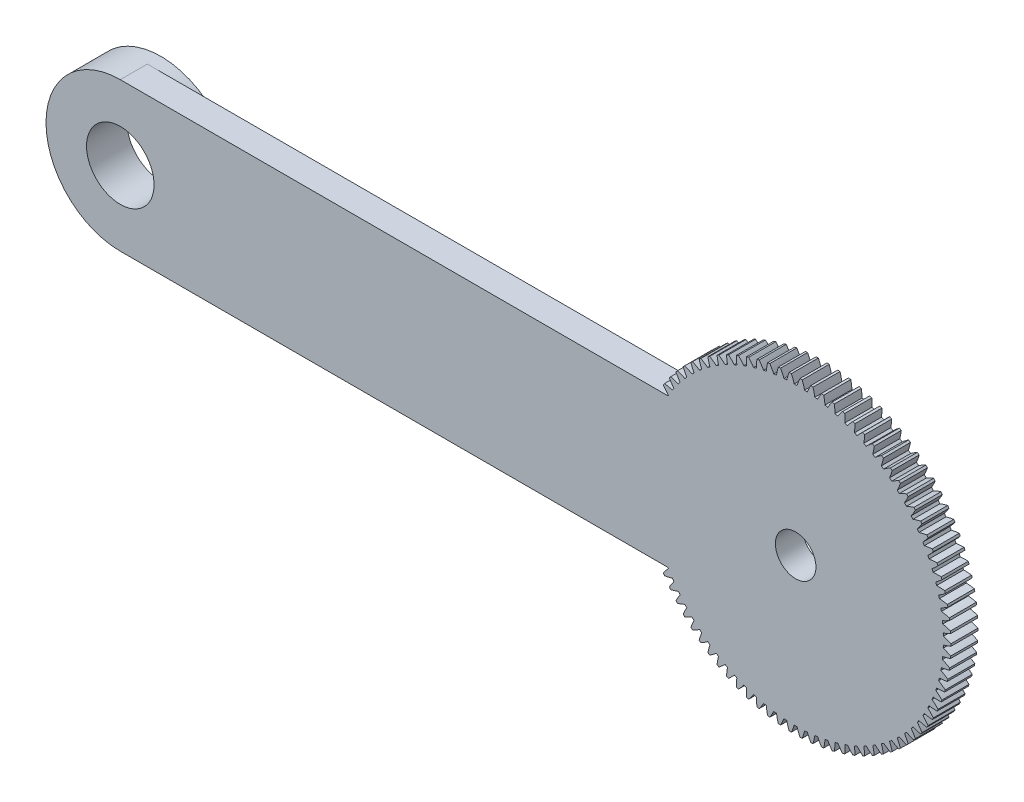
SolidWorks part; units mm, degrees
material "Alumina"
ref_plane "Plane1" through (0, 0, 0) normal (0, 0, 1) x (1, 0, 0)
ref_plane "Plane2" through (0, 0, 0) normal (0, 1, 0) x (1, 0, 0)
ref_plane "Plane3" through (0, 0, 0) normal (1, 0, 0) x (0, 0, -1)
sketch "HoldingSke" plane through (0, 0, 0) normal (0, 1, 0) x (1, 0, 0)
  line L0 (0, 0) -> (0, -2)
  line L1 (-15, 0) -> (100, 0) construction
  line L2 (0, 0) -> (-2.1039, 2.3779)
  line L3 (0, 0) -> (-11.863, 4.5341)
  line L4 (0, 0) -> (0, 8.636)
  line L5 (0, 0) -> (-46.8476, -17.4728)
  line L6 (0, 0) -> (-3.3159, -2.2372)
  line L7 (-2.1039, 2.3779) -> (8.6586, 51.2059)
  line L8 (-76.2, 54.61) -> (-74.4, 54.61)
  line L9 (-71.009, 38.7566) -> (-53.1078, 45.2721)
  line L10 (-76.2, 71.12) -> (104.1128, 71.12)
  line L11 (0, 0) -> (-4, 0)
  line L12 (-76.2, 101.6) -> (-76.181, 101.6)
  line L13 (24.9733, 27.94) -> (52.9518, 28.4284)
  line L14 (24.9733, 27.94) -> (24.9743, 27.94)
  line L15 (24.9733, 27.94) -> (100.4006, 29.5858)
  line L16 (-63.627, -0.5) -> (-12.827, -0.5)
  circle A0 centre (0, 0) radius 5
  circle A1 centre (0, 0) radius 21.874
  circle A2 centre (0, 0) radius 37.5
  circle A3 centre (0, 0) radius 5
  dimension "MHD" = 43.748
  dimension "Hub_dia" = 75
  dimension "Bore" = 10
  dimension "MBD" = 10
  dimension "Num_teeth" = 90
  dimension "Pitch" = 2
  dimension "Overall_len" = 50
  dimension "Show_teeth" = 90
  dimension "Thickness" = 4
  dimension "OAL" = 50.0001
  dimension "T_dim" = 1.8
  dimension "Ap" = 20
  dimension "H" = 19.05
  dimension "Pitch_radius" = 180.3128
  dimension "Width" = 4
  dimension "Backlash" = 0.019
  dimension "Addendum_fac" = 1
  dimension "Dedendum_fac" = 1.25
  dimension "Clearance_fac" = 0.25
  dimension "Dedendum_add" = 0.001
  dimension "Module" = 0.5
sketch "BasProSke" plane through (0, 0, 0) normal (0, 1, 0) x (1, 0, 0)
  line L0 (-10, 0) -> (60, 0) construction
  line L1 (0, 0) -> (0, 23)
  line L2 (0, 0) -> (4, 0)
  line L3 (4, 0) -> (4, 23)
  line L4 (4, 23) -> (0, 23)
  dimension "Thickness" = 4
  dimension "Diameter" = 46
revolve "Base-Revolve" add sketch "BasProSke" angle 360 about L0
sketch "TooCutSke" plane through (0, 0, 0) normal (1, 0, 0) x (0, 0, -1)
  line L1 (0, 0) -> (0, 107) construction
  line L2 (0, 0) -> (-0.4259, 22.496) construction
  line L3 (0, 0) -> (-1.5703, 44.9668) construction
  line L4 (-0.4259, 22.496) -> (-0.7851, 22.4834) construction
  arc A0 (0.2085, 21.873) -> (-0.2085, 21.873) centre (0, 0) ccw
  arc A1 (0.6483, 23.0163) -> (-0.6483, 23.0163) centre (0, 0) ccw
  circle A2 centre (0, 0) radius 22.5 construction
  circle A3 centre (0, 0) radius 21.1431 construction
  arc A4 (-0.2085, 21.873) -> (-0.6483, 23.0163) centre (-8.8088, 19.2207) ccw
  arc A5 (0.6483, 23.0163) -> (0.2085, 21.873) centre (8.8088, 19.2207) ccw
  dimension "Root_dia" = 43.748
  dimension "Overcut_dia" = 46.0508
  dimension "Pitch_dia" = 45
  dimension "Base_dia" = 42.2862
  dimension "Flank_rad" = 9
  dimension "Half_ang" = 2
  dimension "Half_CT" = 0.3594
extrude "ToothCut" cut sketch "TooCutSke" along normal through all
fillet "Breaks" [suppressed] radius 0.01 tangent propagation no
fillet "RootFillets" [suppressed] radius 0.126
pattern_circular "TeethCuts" count 90 every 4 about axis through (-10, 0, 0) along (1, 0, 0) of "ToothCut", "RootFillets", "Breaks"
sketch "HubNeaOneSke" plane through (0, 0, 0) normal (-1, 0, 0) x (0, 0, 1)
  circle A0 centre (0, 0) radius 21.874
  dimension "Diameter" = 43.748
extrude "HubNearOne" [suppressed] add sketch "HubNeaOneSke" along normal blind 46.0001
sketch "HubNeaBotSke" plane through (0, 0, 0) normal (-1, 0, 0) x (0, 0, 1)
  circle A0 centre (0, 0) radius 21.874
  dimension "Diameter" = 43.748
extrude "HubNearBoth" [suppressed] add sketch "HubNeaBotSke" along normal blind 23
ref_plane "FarPln" through (4, 0, 0) normal (1, 0, 0) x (0, 0, -1)
sketch "HubFarSke" plane through (4, 0, 0) normal (1, 0, 0) x (0, 0, -1)
  circle A0 centre (0, 0) radius 21.874
  dimension "Diameter" = 43.748
extrude "HubFar" [suppressed] add sketch "HubFarSke" along normal blind 23
sketch "BorSke" plane through (0, 0, 0) normal (1, 0, 0) x (0, 0, -1)
  circle A0 centre (0, 0) radius 5
  dimension "Diameter" = 10
extrude "Bore" cut sketch "BorSke" along normal mid plane 100.0001
sketch "KeySke" plane through (0, 0, 0) normal (1, 0, 0) x (0, 0, -1)
  line L0 (-2, 0) -> (-2, 6.8)
  line L1 (-2, 6.8) -> (2, 6.8)
  line L2 (2, 6.8) -> (2, 0)
  line L3 (0, 0) -> (0, 34) construction
  line L4 (-2, 0) -> (2, 0)
  dimension "Width" = 4
  dimension "Offset" = 6.8
extrude "Keyway" [suppressed] cut sketch "KeySke" along normal mid plane 100.0001
pattern_circular "Keyway2" [suppressed] count 2 every 90 about axis through (-10, 0, 0) along (1, 0, 0) reverse direction yes
sketch "Sketch1" plane through (0, 0, 0) normal (1, 0, 0) x (0, 0, -1)
  line L0 (0, 0) -> (-100, 0) construction
  line L1 (0, -11) -> (-100, -11)
  line L2 (0, 11) -> (-100, 11)
  arc A0 (0, -11) -> (0, 11) centre (0, 0) ccw
  arc A1 (-100, 11) -> (-100, -11) centre (-100, 0) ccw
  point P3 (-50, 0)
extrude "Boss-Extrude1" add sketch "Sketch1" along normal blind 4 contours L2 A1 L1 A0
sketch "Sketch4" plane through (0, 0, 0) normal (1, 0, 0) x (0, 0, -1)
  circle A0 centre (0, 0) radius 3
extrude "Cut-Extrude4" cut sketch "Sketch4" along normal through all
move or copy body "Body-Move/Copy1" bodies to move or copy 106 copy no rotation origin (2, 0, 94) rotation axis (0, 1, 0) rotation angle 90
move or copy body "Body-Move/Copy2" bodies to move or copy 107 copy no rotation origin (2, 0, 0) rotation axis (0, 0, 1) rotation angle 180
sketch "Sketch5" plane through (0, 0, 92) normal (0, 0, -1) x (-1, 0, 0)
  circle A5 centre (4, 0) radius 11
extrude "Boss-Extrude2" add sketch "Sketch5" along normal blind 2
ref_axis "Axis1" through (96, 0, 63.756) along (0, 0, 1)
sketch "Sketch6" plane through (0, 0, 90) normal (0, 0, -1) x (-1, 0, 0)
  circle A0 centre (4, 0) radius 5
  point P3 (0, 0)
  point P4 (0, 0)
  point P5 (0, 0)
  point P9 (0, 0)
extrude "Cut-Extrude5" cut sketch "Sketch6" against normal blind 10
equation "' \"Module@HoldingSke\" = 6.35"
equation "' \"Num_teeth@HoldingSke\" = 12"
equation "' \"Ap@HoldingSke\" =  20"
equation "' \"Ap@HoldingSke\" = 20"
equation "' \"Width@HoldingSke\" = 0.5 * 25.4"
equation "' \"Hub_dia@HoldingSke\"= 1 * 25.4"
equation "' \"Hub_dia@HoldingSke\" = 1 * 25.4"
equation "' \"Overall_len@HoldingSke\" = 1.0 * 25.4"
equation "' \"Bore@HoldingSke\" = 0.75 * 25.4"
equation "' \"T_dim@HoldingSke\" = 0.1 * 25.4"
equation "' \"Width@KeySke\" = 0.25 * 25.4"
equation "' \"Show_teeth@HoldingSke\" = 13"
equation "' \"Backlash@HoldingSke\" = 0.009 * 25.4"
equation "' \"Addendum_fac@HoldingSke\" = 1.0"
equation "' \"Dedendum_fac@HoldingSke\" = 1.25"
equation "' \"Dedendum_add@HoldingSke\" = 0.00005 * 25.4"
equation "' \"Clearance_fac@HoldingSke\" = 0.25"
equation "\"Pitch@HoldingSke\" = 1 / \"Module@HoldingSke\""
equation "\"Overcut_dia@TooCutSke\" = (\"Num_teeth@HoldingSke\" + 2 * \"Addendum_fac@HoldingSke\") / \"Pitch@HoldingSke\" + 0.002 * 25.4"
equation "\"Pitch_dia@TooCutSke\" = \"Num_teeth@HoldingSke\" / \"Pitch@HoldingSke\""
equation "\"Base_dia@TooCutSke\" = \"Num_teeth@HoldingSke\" / \"Pitch@HoldingSke\" * cos((\"Ap@HoldingSke\"  * 3.14159265 / 180))"
equation "\"Root_dia@TooCutSke\" = (\"Num_teeth@HoldingSke\" + 2) / \"Pitch@HoldingSke\" - 2 * (\"Addendum_fac@HoldingSke\" + \"Dedendum_fac@HoldingSke\") / \"Pitch@HoldingSke\" - \"Dedendum_add@HoldingSke\" * 2"
equation "\"Half_ang@TooCutSke\" = 180 / \"Num_teeth@HoldingSke\""
equation "\"Half_CT@TooCutSke\" = \"Num_teeth@HoldingSke\" / \"Pitch@HoldingSke\" * sin((3.14159265 / 2 / \"Num_teeth@HoldingSke\")) / 2 - 7 * \"Backlash@HoldingSke\" / 4"
equation "\"Flank_rad@TooCutSke\" = \"Num_teeth@HoldingSke\" / \"Pitch@HoldingSke\" / 5"
equation "\"Radius@RootFillets\" = \"Clearance_fac@HoldingSke\" / \"Pitch@HoldingSke\" + \"Dedendum_add@HoldingSke\""
equation "\"Break_rad@Breaks\" = 0.02 / \"Pitch@HoldingSke\""
equation "\"Thickness@HoldingSke\" = \"Width@HoldingSke\""
equation "\"OAL@HoldingSke\" = \"Thickness@HoldingSke\""
equation "\"MHD@HoldingSke\" = (\"Num_teeth@HoldingSke\" + 2) / \"Pitch@HoldingSke\" - 2 * (\"Addendum_fac@HoldingSke\" + \"Dedendum_fac@HoldingSke\")  / \"Pitch@HoldingSke\" - \"Dedendum_add@HoldingSke\" * 2"
equation "\"MBD@HoldingSke\" = (\"Num_teeth@HoldingSke\" + 2) / \"Pitch@HoldingSke\" - 2 * (\"Addendum_fac@HoldingSke\" + \"Dedendum_fac@HoldingSke\")  / \"Pitch@HoldingSke\" - \"Dedendum_add@HoldingSke\" * 2 - 0.002 * 25.4"
equation "\"MHD@HoldingSke\" = ((sgn( \"MHD@HoldingSke\" - \"Hub_dia@HoldingSke\" )-1)*( \"MHD@HoldingSke\" - \"Hub_dia@HoldingSke\" ))/-2+ \"Hub_dia@HoldingSke\""
equation "\"MBD@HoldingSke\" = ((sgn( \"MBD@HoldingSke\" - \"Bore@HoldingSke\" )-1)*( \"MBD@HoldingSke\" - \"Bore@HoldingSke\" ))/-2+ \"Bore@HoldingSke\""
equation "\"OAL@HoldingSke\" = ((sgn( \"OAL@HoldingSke\" - \"Overall_len@HoldingSke\" )+1)*( \"OAL@HoldingSke\" - \"Overall_len@HoldingSke\" ))/2 + \"Overall_len@HoldingSke\" + 0.000002 * 25.4"
equation "\"Num_teeth@TeethCuts\" = int( \"Show_teeth@HoldingSke\" ) + 1"
equation "\"Num_teeth@TeethCuts\" = ((sgn( \"Num_teeth@TeethCuts\" - \"Num_teeth@HoldingSke\" )-1)*( \"Num_teeth@TeethCuts\" - \"Num_teeth@HoldingSke\" ))/-2+ \"Num_teeth@HoldingSke\""
equation "\"Num_teeth@TeethCuts\" = ((sgn( \"Num_teeth@TeethCuts\" - 2.0)+1)*( \"Num_teeth@TeethCuts\" - 2.0))/2 +2.0"
equation "\"Angle@TeethCuts\" = 360.0 / \"Num_teeth@HoldingSke\""
equation "\"Diameter@BasProSke\" = (\"Num_teeth@HoldingSke\" + 2 * \"Addendum_fac@HoldingSke\") / \"Pitch@HoldingSke\""
equation "\"Thickness@BasProSke\"  = \"Thickness@HoldingSke\""
equation "' \"Fillet_rad@BasProSke\" =  \"Thickness@HoldingSke\" * 0.05"
equation "' \"Fillet_rad@BasProSke\" = \"Thickness@HoldingSke\" * 0.05"
equation "\"MHD@HoldingSke\" = ((sgn( \"MHD@HoldingSke\" - \"Root_dia@TooCutSke\" )-1)*( \"MHD@HoldingSke\" - \"Root_dia@TooCutSke\" ))/-2+ \"Root_dia@TooCutSke\""
equation "\"Diameter@HubNeaOneSke\" = \"MHD@HoldingSke\""
equation "\"Length@HubNearOne\" = \"OAL@HoldingSke\" - \"Thickness@BasProSke\""
equation "\"Diameter@HubNeaBotSke\" = \"MHD@HoldingSke\""
equation "\"Length@HubNearBoth\" = ( \"OAL@HoldingSke\" - \"Thickness@BasProSke\" ) / 2.0"
equation "\"Thickness@FarPln\" = \"Thickness@BasProSke\""
equation "\"Diameter@HubFarSke\" = \"MHD@HoldingSke\""
equation "\"Length@HubFar\" = ( \"OAL@HoldingSke\" - \"Thickness@BasProSke\" ) / 2.0"
equation "\"Diameter@BorSke\" = \"MBD@HoldingSke\""
equation "\"D1@Bore\" = \"OAL@HoldingSke\" * 2.0"
equation "\"D1@Keyway\" = \"OAL@HoldingSke\" * 2.0"
equation "\"Offset@KeySke\" = \"T_dim@HoldingSke\" + \"MBD@HoldingSke\" / 2.0"
